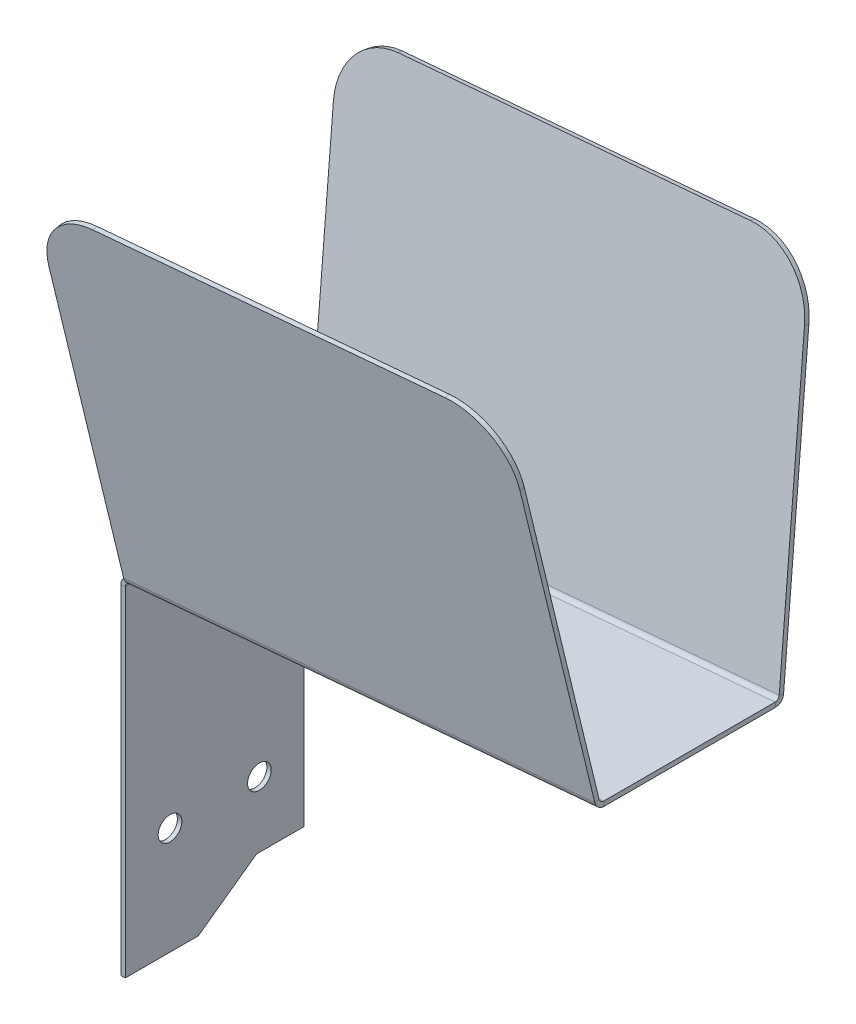
SolidWorks part; units mm, degrees
note: The reader was unsure of these and kept them because the rebuilt part matched: flange length of "Edge-Flange1", "Edge-Flange2".
material "Plain Carbon Steel"
ref_plane "Front Plane" through (0, 0, 0) normal (0, 0, 1) x (1, 0, 0)
ref_plane "Top Plane" through (0, 0, 0) normal (0, 1, 0) x (1, 0, 0)
ref_plane "Right Plane" through (0, 0, 0) normal (1, 0, 0) x (0, 0, -1)
sketch "Sketch1" plane through (0, 0, 0) normal (1, 0, 0) x (0, 0, -1)
  line L1 (-15, -28.75) -> (15, -28.75)
  line L2 (-15, -28.75) -> (-15, 28.75)
  line L3 (-15, 28.75) -> (15, 28.75)
  line L4 (15, -28.75) -> (15, 28.75)
  line L5 (-15, -28.75) -> (15, 28.75) construction
  line L6 (-15, 28.75) -> (15, -28.75) construction
  point P0 (0, 0)
  dimension "D1" = 30
  dimension "D2" = 57.5
base flange "Base-Flange1" sketch "Sketch1" thickness 0.7366 reverse thickness direction no parameters "D1"=0.7366
edge flange "Edge-Flange1" sketch "Sketch8" flange angle 95 flange length 80 flange position material outside bend radius 0.7366 thickness 0.7366 relief rectangular parameters "D6"=10
sketch "Sketch8" plane through (0, 28.75, 0) normal (0.0872, -0.9962, 0) x (0, 0, -1)
  line L1 (15, 0) -> (-15, 0) construction
  line L2 (-15, 0) -> (-15, 80)
  line L3 (-15, 80) -> (15, 80)
  line L4 (15, 80) -> (15, 0)
  line L5 (15, 0) -> (-15, 0)
  dimension "D1" = 80
bend "EdgeBend1" bend radius 0.7366 bend angle 85 parameters "D5"=1
edge flange "Edge-Flange2" sketch "Sketch11" flange angle 100 flange length 59 flange position material outside bend radius 0.7366 thickness 0.7366 relief none parameters "D6"=10
sketch "Sketch11" plane through (-2.5604, 29.2654, 15) normal (-0.0151, 0.173, -0.9848) x (-0.9962, -0.0872, 0)
  line L1 (-3.1807, 0) -> (-82.5057, 0) construction
  line L2 (-82.5057, 0) -> (-82.5057, 59)
  line L3 (-82.5057, 59) -> (-3.1807, 59)
  line L4 (-3.1807, 59) -> (-3.1807, 0)
  line L5 (-3.1807, 0) -> (-82.5057, 0)
  dimension "D1" = 59
bend "EdgeBend2" bend radius 0.7366 bend angle 80 parameters "D5"=2
mirror "Mirror1" about plane through (0, 0, 0) normal (0, 0, 1) of "Edge-Flange2"
bend "MirrorBend1" bend radius 0.7366 bend angle 80 parameters "D5"=3
fillet "Fillet1" radius 10 4 edges at (-4.4503, 87.3615, -25.6079) (-4.4503, 87.3615, 25.6079) (74.5729, 94.2751, -25.6079) (74.5729, 94.2751, 25.6079)
sketch "Sketch13" plane through (0, 0, 0) normal (1, 0, 0) x (0, 0, -1)
  line L0 (15, -21.75) -> (7, -21.75)
  line L1 (15, -28.75) -> (15, 28.075) construction
  line L2 (7, -21.75) -> (-2.7468, -28.75)
  line L3 (-15, -28.75) -> (15, -28.75) construction
  dimension "D1" = 7
  dimension "D2" = 8
  dimension "D3" = 12
extrude "Cut-Extrude1" cut sketch "Sketch13" against normal through all and the other way through all normal cut yes
sketch "Sketch14" plane through (0, 0, 0) normal (1, 0, 0) x (0, 0, -1)
  line L0 (-15, -28.75) -> (-2.7468, -28.75) construction
  line L1 (0, 0) -> (0, -24.4819) construction
  line L2 (-15, 28.075) -> (-15, -28.75) construction
  circle A0 centre (-7.5, -10.75) radius 1.9844
  circle A1 centre (7.5, -10.75) radius 1.9844
  dimension "D1" = 3.9688
  dimension "D2" = 3.9688
  dimension "D3" = 7.5
  dimension "D4" = 18
extrude "Cut-Extrude2" cut sketch "Sketch14" against normal through all normal cut yes
sketch "Bend-Lines1" [suppressed] plane through (0, 0, 0) normal (0, 1, 0) x (1, 0, 0)
sketch "Bounding-Box1" [suppressed] plane through (0, 0, 0) normal (0, 1, 0) x (1, 0, 0)
sheet metal parameters "Sheet-Metal3" thickness 0.7366 parameters "D1"=0.7366
flat pattern "Flat-Pattern3" [suppressed]
sketch "Bend-Lines2" plane through (0, 0, 0) normal (0, 1, 0) x (1, 0, 0)
sketch "Bounding-Box2" [suppressed] plane through (0, 0, 0) normal (0, 1, 0) x (1, 0, 0)
sheet metal parameters "Sheet-Metal4" thickness 0.7366 parameters "D1"=0.7366
flat pattern "Flat-Pattern3" [suppressed]
sketch "Bend-Lines2" plane through (0, 0, 0) normal (0, 1, 0) x (1, 0, 0)
sketch "Bounding-Box2" [suppressed] plane through (0, 0, 0) normal (0, 1, 0) x (1, 0, 0)
bend of the flat pattern "Flatten-<EdgeBend1>1"
sheet metal parameters "Sheet-Metal5" thickness 0.7366 parameters "D1"=0.7366
flat pattern "Flat-Pattern3" [suppressed]
sketch "Bend-Lines2" plane through (0, 0, 0) normal (0, 1, 0) x (1, 0, 0)
sketch "Bounding-Box2" [suppressed] plane through (0, 0, 0) normal (0, 1, 0) x (1, 0, 0)
bend of the flat pattern "Flatten-<EdgeBend1>1"
bend of the flat pattern "Flatten-<EdgeBend2>1"
sheet metal parameters "Sheet-Metal6" thickness 0.7366 parameters "D1"=0.7366
flat pattern "Flat-Pattern3" [suppressed]
sketch "Bend-Lines2" plane through (0, 0, 0) normal (0, 1, 0) x (1, 0, 0)
sketch "Bounding-Box2" [suppressed] plane through (0, 0, 0) normal (0, 1, 0) x (1, 0, 0)
bend of the flat pattern "Flatten-<EdgeBend1>1"
bend of the flat pattern "Flatten-<EdgeBend2>1"
bend of the flat pattern "Flatten-<MirrorBend1>1"
sheet metal parameters "Sheet-Metal7" thickness 0.7366 parameters "D1"=0.7366
flat pattern "Flat-Pattern3" [suppressed]
sketch "Bend-Lines2" plane through (0, 0, 0) normal (0, 1, 0) x (1, 0, 0)
sketch "Bounding-Box2" [suppressed] plane through (0, 0, 0) normal (0, 1, 0) x (1, 0, 0)
bend of the flat pattern "Flatten-<EdgeBend1>1"
bend of the flat pattern "Flatten-<EdgeBend2>1"
bend of the flat pattern "Flatten-<MirrorBend1>1"
sheet metal parameters "Sheet-Metal8" thickness 0.7366 parameters "D1"=0.7366
flat pattern "Flat-Pattern3"
sketch "Bend-Lines2" plane through (0, 0, 0) normal (1, 0, 0) x (0, 0, -1)
  line L0 (15.1533, 29.7142) -> (15.1533, 109.0392) construction
  line L1 (-15.1533, 109.0392) -> (-15.1533, 29.7142) construction
  line L2 (-15, 28.8946) -> (15, 28.8946) construction
  line L3 (15.1533, 29.7142) -> (15.1533, 109.0392) construction
  line L4 (-15.1533, 109.0392) -> (-15.1533, 29.7142) construction
  line L5 (-15, 28.8946) -> (15, 28.8946) construction
sketch3d "Bounding-Box2" [suppressed]
  line L0 (74.3066, 109.0392, 0) -> (-74.3066, 109.0392, 0) construction
  line L1 (74.3066, -28.75, 0) -> (-74.3066, -28.75, 0) construction
  line L2 (74.3066, 109.0392, 0) -> (74.3066, -28.75, 0) construction
  line L3 (-74.3066, 109.0392, 0) -> (-74.3066, -28.75, 0) construction
bend of the flat pattern "Flatten-<EdgeBend1>1"
bend of the flat pattern "Flatten-<EdgeBend2>1"
bend of the flat pattern "Flatten-<MirrorBend1>1"
